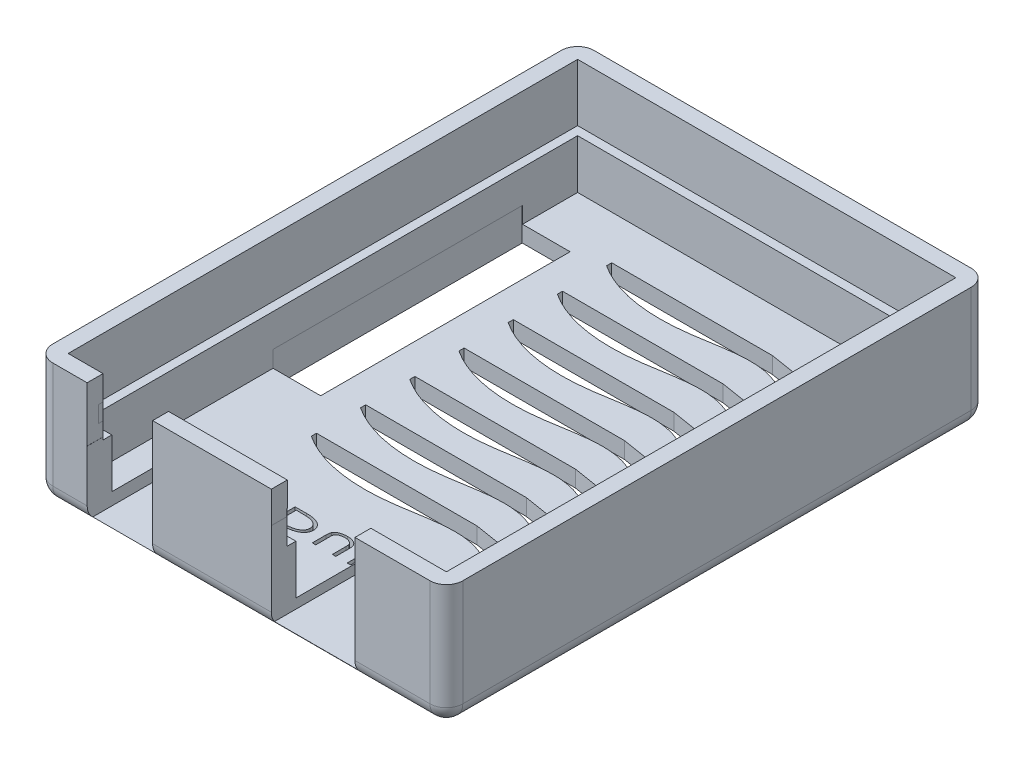
SolidWorks part; units mm, degrees
ref_plane "Front Plane" through (0, 0, 0) normal (0, 0, 1) x (1, 0, 0)
ref_plane "Top Plane" through (0, 0, 0) normal (0, 1, 0) x (1, 0, 0)
ref_plane "Right Plane" through (0, 0, 0) normal (1, 0, 0) x (0, 0, -1)
sketch "Sketch1" plane through (0, 0, 0) normal (0, 1, 0) x (1, 0, 0)
  line L1 (-31.75, 41.91) -> (31.75, 41.91)
  line L2 (-31.75, 41.91) -> (-31.75, -41.91)
  line L3 (-31.75, -41.91) -> (31.75, -41.91)
  line L4 (31.75, 41.91) -> (31.75, -41.91)
  line L5 (-31.75, 41.91) -> (31.75, -41.91) construction
  line L6 (-31.75, -41.91) -> (31.75, 41.91) construction
  point P0 (0, 0)
  dimension "D1" = 63.5
  dimension "D2" = 83.82
extrude "Boss-Extrude1" add sketch "Sketch1" along normal blind 12.7
sketch "Sketch3" plane through (0, 12.7, 0) normal (0, 1, 0) x (1, 0, 0)
  line L1 (27.94, -38.1) -> (-27.94, -38.1)
  line L2 (27.94, -38.1) -> (27.94, 38.1)
  line L3 (27.94, 38.1) -> (-27.94, 38.1)
  line L4 (-27.94, -38.1) -> (-27.94, 38.1)
  line L5 (27.94, -38.1) -> (-27.94, 38.1) construction
  line L6 (27.94, 38.1) -> (-27.94, -38.1) construction
  point P0 (0, 0)
  dimension "D1" = 76.2
  dimension "D2" = 55.88
extrude "Cut-Extrude1" cut sketch "Sketch3" against normal blind 15.24
sketch "Sketch4" plane through (0, 12.7, 0) normal (0, 1, 0) x (1, 0, 0)
  line L0 (29.2862, -39.4462) -> (29.2862, 39.4462)
  line L1 (31.75, -41.91) -> (-31.75, -41.91)
  line L2 (31.75, -41.91) -> (31.75, 41.91)
  line L3 (31.75, 41.91) -> (-31.75, 41.91)
  line L4 (-31.75, -41.91) -> (-31.75, 41.91)
  line L5 (29.2862, 39.4462) -> (-29.2862, 39.4462)
  line L6 (-29.2862, -39.4462) -> (-29.2862, 39.4462)
  line L7 (29.2862, -39.4462) -> (-29.2862, -39.4462)
  dimension "D1" = 2.4638
extrude "Boss-Extrude2" add sketch "Sketch4" along normal blind 3.81
sketch "Sketch5" plane through (0, 0, 0) normal (0, -1, 0) x (-1, 0, 0)
  line L1 (31.75, 41.91) -> (-31.75, 41.91)
  line L2 (31.75, 41.91) -> (31.75, -41.91)
  line L3 (31.75, -41.91) -> (-31.75, -41.91)
  line L4 (-31.75, 41.91) -> (-31.75, -41.91)
extrude "Boss-Extrude3" add sketch "Sketch5" along normal blind 2.54
ref_plane "Plane1" through (27.94, 0, 38.1) normal (1, 0, 0) x (0, 0, -1)
sketch "Sketch8" plane through (0, 0, 41.91) normal (0, 0, 1) x (1, 0, 0)
  line L1 (17.5873, -0.2318) -> (4.632, -0.2318)
  line L2 (17.5873, -0.2318) -> (17.5873, 11.6189)
  line L3 (17.5873, 11.6189) -> (4.632, 11.6189)
  line L4 (4.632, -0.2318) -> (4.632, 11.6189)
extrude "Cut-Extrude2" cut sketch "Sketch8" against normal blind 10.16
sketch "Sketch9" plane through (0, 0, 41.91) normal (0, 0, 1) x (1, 0, 0)
  line L1 (-13.7438, 12.0602) -> (-23.8766, 12.0602)
  line L2 (-13.7438, 12.0602) -> (-13.7438, -0.6398)
  line L3 (-13.7438, -0.6398) -> (-23.8766, -0.6398)
  line L4 (-23.8766, 12.0602) -> (-23.8766, -0.6398)
  dimension "D1" = 12.7
extrude "Cut-Extrude3" cut sketch "Sketch9" against normal blind 15.24
sketch "Sketch12" plane through (0, 0, 41.91) normal (0, 0, 1) x (1, 0, 0)
  line L0 (17.5873, -0.2318) -> (17.5873, 11.6189) construction
  line L1 (17.5873, 9.3661) -> (4.645, 9.3661)
  line L2 (17.5873, 9.3661) -> (17.5873, 18.5557)
  line L3 (17.5873, 18.5557) -> (4.645, 18.5557)
  line L4 (4.645, 9.3661) -> (4.645, 18.5557)
  line L5 (-13.7438, -0.6398) -> (-13.7438, 12.0602) construction
  line L6 (-13.7438, 8.0218) -> (-23.8897, 8.0218)
  line L7 (-13.7438, 8.0218) -> (-13.7438, 17.5809)
  line L8 (-13.7438, 17.5809) -> (-23.8897, 17.5809)
  line L9 (-23.8897, 8.0218) -> (-23.8897, 17.5809)
extrude "Cut-Extrude6" cut sketch "Sketch12" against normal blind 2.54
sketch "Sketch13" plane through (0, 12.7, 0) normal (0, 1, 0) x (1, 0, 0)
  line L1 (4.6364, -39.5719) -> (17.609, -39.5719)
  line L2 (4.6364, -39.5719) -> (4.6364, -37.766)
  line L3 (4.6364, -37.766) -> (17.609, -37.766)
  line L4 (17.609, -39.5719) -> (17.609, -37.766)
extrude "Cut-Extrude7" cut sketch "Sketch13" against normal blind 2.54
sketch "Sketch15" plane through (0, 12.7, 0) normal (0, 1, 0) x (1, 0, 0)
  line L1 (-13.7438, -40.1592) -> (-23.8918, -40.1592)
  line L2 (-13.7438, -40.1592) -> (-13.7438, -37.7041)
  line L3 (-13.7438, -37.7041) -> (-23.8918, -37.7041)
  line L4 (-23.8918, -40.1592) -> (-23.8918, -37.7041)
extrude "Cut-Extrude8" cut sketch "Sketch15" against normal blind 2.54
sketch "Sketch16" plane through (0, 12.7, 0) normal (0, 1, 0) x (1, 0, 0)
  line L0 (-29.2862, 39.4462) -> (-29.2862, -39.4462) construction
  line L1 (29.2862, -39.4462) -> (-29.2862, -39.4462)
  line L2 (29.2862, -39.4462) -> (29.2862, 39.4462)
  line L3 (29.2862, 39.4462) -> (-29.2862, 39.4462)
  line L4 (-29.2862, -39.4462) -> (-29.2862, 39.4462)
  line L5 (29.2862, 39.4462) -> (-29.2862, 39.4462) construction
extrude "Cut-Extrude9" cut sketch "Sketch16" against normal blind 5.08
sketch "Sketch17" plane through (0, 0, 41.91) normal (0, 0, 1) x (1, 0, 0)
  line L1 (-23.8766, -0.6398) -> (-13.743, -0.6398)
  line L2 (-23.8766, -0.6398) -> (-23.8766, -1.9098)
  line L3 (-23.8766, -1.9098) -> (-13.743, -1.9098)
  line L4 (-13.743, -0.6398) -> (-13.743, -1.9098)
  line L5 (4.632, -0.2318) -> (17.5873, -0.2318)
  line L6 (4.632, -0.2318) -> (4.632, -1.5018)
  line L7 (4.632, -1.5018) -> (17.5873, -1.5018)
  line L8 (17.5873, -0.2318) -> (17.5873, -1.5018)
  dimension "D1" = 1.27
  dimension "D2" = 1.27
extrude "Cut-Extrude10" cut sketch "Sketch17" against normal blind 12.7
sketch "Sketch18" plane through (0, 0, 0) normal (0, 1, 0) x (1, 0, 0)
  line L1 (4.632, -31.75) -> (17.625, -31.75)
  line L2 (4.632, -31.75) -> (4.632, -26.67)
  line L3 (4.632, -26.67) -> (17.625, -26.67)
  line L4 (17.625, -31.75) -> (17.625, -26.67)
  dimension "D1" = 5.08
extrude "Cut-Extrude11" cut sketch "Sketch18" against normal up to vertex (1.5018 mm away) up to point (4.632, -1.5018, 29.21)
sketch "Sketch19" plane through (0, -0.6398, 0) normal (0, 1, 0) x (1, 0, 0)
  line L1 (-23.8766, -29.21) -> (-13.7438, -29.21)
  line L2 (-23.8766, -29.21) -> (-23.8766, -26.67)
  line L3 (-23.8766, -26.67) -> (-13.7438, -26.67)
  line L4 (-13.7438, -29.21) -> (-13.7438, -26.67)
extrude "Cut-Extrude12" cut sketch "Sketch19" against normal blind 1.27
sketch "Sketch21" plane through (0, -2.54, 0) normal (0, -1, 0) x (-1, 0, 0)
  line L0 (20.5724, -9.0606) -> (20.5724, 29.5721)
  line L1 (-27.8861, -18.3171) -> (-27.8861, 29.6515)
  line L5 (20.5724, 29.5721) -> (27.9874, 29.5721)
  line L6 (27.9874, -9.0606) -> (27.9874, 29.5721)
  line L7 (20.5724, -9.0606) -> (27.9874, -9.0606)
  line L9 (-27.8861, 29.6515) -> (-20.284, 29.6515)
  line L10 (-20.284, -18.3171) -> (-20.284, 29.6515)
  line L11 (-27.8861, -18.3171) -> (-20.284, -18.3171)
extrude "Cut-Extrude13" cut sketch "Sketch21" against normal blind 5.08
sketch "Sketch22" plane through (0, -2.54, 0) normal (0, -1, 0) x (1, 0, 0)
  line L0 (13.9602, 18.3641) -> (13.9602, 15.2066)
  line L1 (13.9602, 15.2066) -> (8.9965, 14.4068)
  line L2 (8.9965, 14.4068) -> (-15.871, 14.4068)
  line L3 (-15.871, 14.4068) -> (-15.871, 15.2066)
  line L4 (13.9602, 10.7441) -> (13.9602, 7.5866)
  line L5 (13.9602, 7.5866) -> (8.9965, 6.7868)
  line L6 (8.9965, 6.7868) -> (-15.871, 6.7868)
  line L7 (-15.871, 6.7868) -> (-15.871, 7.5866)
  line L8 (13.9602, 3.1241) -> (13.9602, -0.0334)
  line L9 (13.9602, -0.0334) -> (8.9965, -0.8332)
  line L10 (8.9965, -0.8332) -> (-15.871, -0.8332)
  line L11 (-15.871, -0.8332) -> (-15.871, -0.0334)
  line L12 (13.9602, -4.4959) -> (13.9602, -7.6534)
  line L13 (13.9602, -7.6534) -> (8.9965, -8.4532)
  line L14 (8.9965, -8.4532) -> (-15.871, -8.4532)
  line L15 (-15.871, -8.4532) -> (-15.871, -7.6534)
  line L16 (13.9602, -12.1159) -> (13.9602, -15.2734)
  line L17 (13.9602, -15.2734) -> (8.9965, -16.0732)
  line L18 (8.9965, -16.0732) -> (-15.871, -16.0732)
  line L19 (-15.871, -16.0732) -> (-15.871, -15.2734)
  line L20 (13.9602, -19.7359) -> (13.9602, -22.8934)
  line L21 (13.9602, -22.8934) -> (8.9965, -23.6932)
  line L22 (8.9965, -23.6932) -> (-15.871, -23.6932)
  line L23 (-15.871, -23.6932) -> (-15.871, -22.8934)
  line L24 (13.9602, -27.3559) -> (13.9602, -30.5134)
  line L25 (13.9602, -30.5134) -> (8.9965, -31.3132)
  line L26 (8.9965, -31.3132) -> (-15.871, -31.3132)
  line L27 (-15.871, -31.3132) -> (-15.871, -30.5134)
  spline S0 degree 3 poles (13.9602, 18.3641) (9.2068, 15.5936) (-0.809, 19.1941) (-11.6389, 17.9931) (-15.871, 15.2066) knots 0 0 0 0 0.502363 1 1 1 1
  spline S1 degree 3 poles (13.9602, 10.7441) (9.2068, 7.9736) (-0.809, 11.5741) (-11.6389, 10.3731) (-15.871, 7.5866) knots 0 0 0 0 0.502363 1 1 1 1
  spline S2 degree 3 poles (13.9602, 3.1241) (9.2068, 0.3536) (-0.809, 3.9541) (-11.6389, 2.7531) (-15.871, -0.0334) knots 0 0 0 0 0.502363 1 1 1 1
  spline S3 degree 3 poles (13.9602, -4.4959) (9.2068, -7.2664) (-0.809, -3.6659) (-11.6389, -4.8669) (-15.871, -7.6534) knots 0 0 0 0 0.502363 1 1 1 1
  spline S4 degree 3 poles (13.9602, -12.1159) (9.2068, -14.8864) (-0.809, -11.2859) (-11.6389, -12.4869) (-15.871, -15.2734) knots 0 0 0 0 0.502363 1 1 1 1
  spline S5 degree 3 poles (13.9602, -19.7359) (9.2068, -22.5064) (-0.809, -18.9059) (-11.6389, -20.1069) (-15.871, -22.8934) knots 0 0 0 0 0.502363 1 1 1 1
  spline S6 degree 3 poles (13.9602, -27.3559) (9.2068, -30.1264) (-0.809, -26.5259) (-11.6389, -27.7269) (-15.871, -30.5134) knots 0 0 0 0 0.502363 1 1 1 1
  dimension "D1" = 7
extrude "Cut-Extrude14" cut sketch "Sketch22" against normal blind 5.08
fillet "Fillet1" radius 2.54 4 edges at (0, -2.54, -41.91) (-31.75, -2.54, 0) (0, -2.54, 41.91) (31.75, -2.54, 0)
sketch "Sketch23" plane through (0, -2.54, 0) normal (0, -1, 0) x (1, 0, 0)
  text T0 "ARDUINO" font "Century Gothic" height 3.5
extrude "Cut-Extrude17" cut sketch "Sketch23" against normal blind 5.08
fillet "Fillet2" radius 2.54 8 edges at (31.0061, -1.7961, 41.1661) (31.0061, -1.7961, -41.1661) (-31.0061, -1.7961, -41.1661) (-31.0061, -1.7961, 41.1661) (31.75, 8.255, 41.91) (31.75, 8.255, -41.91) (-31.75, 8.255, -41.91) (-31.75, 8.255, 41.91)
